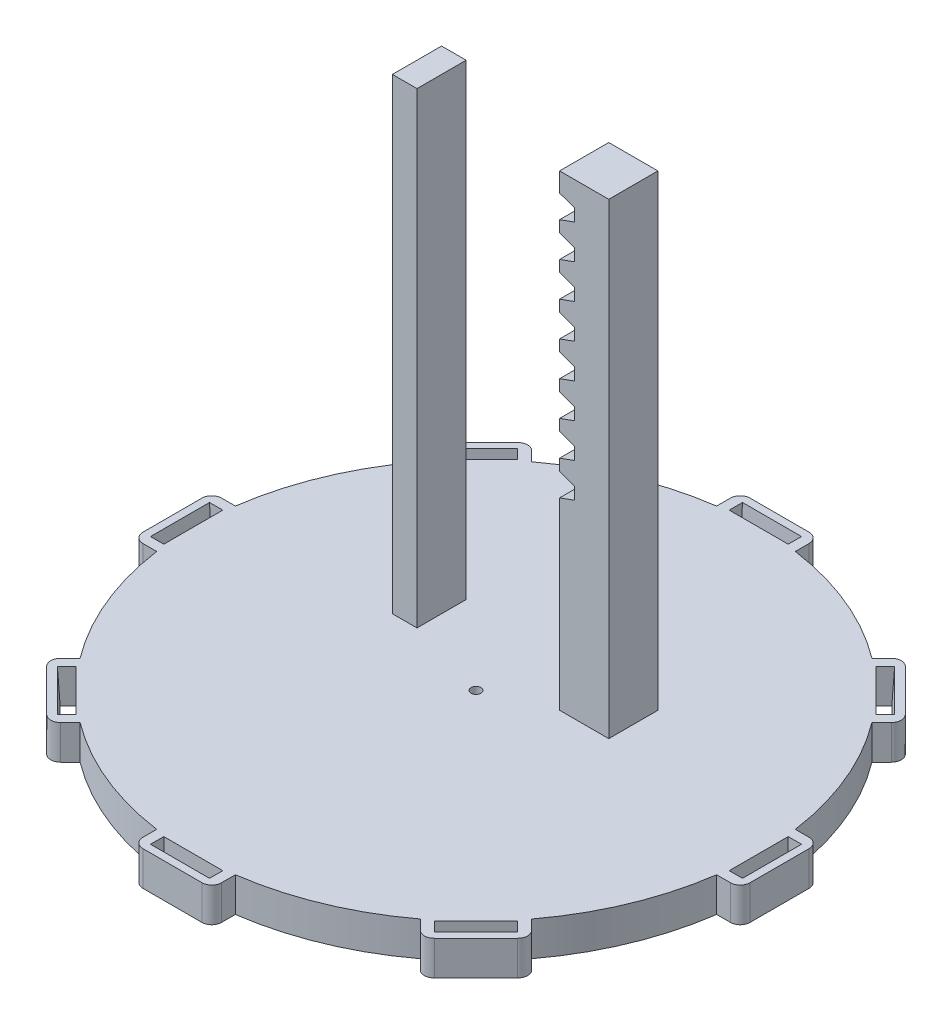
SolidWorks part; units mm, degrees
ref_plane "Front Plane" through (0, 0, 0) normal (0, 0, 1) x (1, 0, 0)
ref_plane "Top Plane" through (0, 0, 0) normal (0, 1, 0) x (1, 0, 0)
ref_plane "Right Plane" through (0, 0, 0) normal (1, 0, 0) x (0, 0, -1)
sketch "Sketch1" plane through (0, 0, 0) normal (0, 1, 0) x (1, 0, 0)
  line L0 (-8, 56.9408) -> (-8, 59.7408)
  line L1 (0, 57.5) -> (0, -57.5) construction
  line L2 (8, 56.9408) -> (8, 59.7408)
  line L3 (-6, 61.7408) -> (6, 61.7408)
  line L4 (39.4147, 47.8999) -> (47.8999, 39.4147)
  line L9 (34.6063, 45.9201) -> (36.5862, 47.8999)
  line L10 (45.9201, 34.6063) -> (47.8999, 36.5862)
  line L15 (61.7408, 6) -> (61.7408, -6)
  line L16 (56.9408, 8) -> (59.7408, 8)
  line L17 (56.9408, -8) -> (59.7408, -8)
  line L22 (47.8999, -39.4147) -> (39.4147, -47.8999)
  line L23 (45.9201, -34.6063) -> (47.8999, -36.5862)
  line L24 (34.6063, -45.9201) -> (36.5862, -47.8999)
  line L29 (6, -61.7408) -> (-6, -61.7408)
  line L30 (8, -56.9408) -> (8, -59.7408)
  line L31 (-8, -56.9408) -> (-8, -59.7408)
  line L36 (-39.4147, -47.8999) -> (-47.8999, -39.4147)
  line L37 (-34.6063, -45.9201) -> (-36.5862, -47.8999)
  line L38 (-45.9201, -34.6063) -> (-47.8999, -36.5862)
  line L43 (-61.7408, -6) -> (-61.7408, 6)
  line L44 (-56.9408, -8) -> (-59.7408, -8)
  line L45 (-56.9408, 8) -> (-59.7408, 8)
  line L50 (-47.8999, 39.4147) -> (-39.4147, 47.8999)
  line L51 (-45.9201, 34.6063) -> (-47.8999, 36.5862)
  line L52 (-34.6063, 45.9201) -> (-36.5862, 47.8999)
  arc A0 (-8, 56.9408) -> (-34.6063, 45.9201) centre (0, 0) ccw
  arc A1 (6, 61.7408) -> (8, 59.7408) centre (6, 59.7408) cw
  arc A2 (-6, 61.7408) -> (-8, 59.7408) centre (-6, 59.7408) ccw
  arc A3 (39.4147, 47.8999) -> (36.5862, 47.8999) centre (38.0005, 46.4857) ccw
  arc A4 (47.8999, 39.4147) -> (47.8999, 36.5862) centre (46.4857, 38.0005) cw
  arc A5 (61.7408, 6) -> (59.7408, 8) centre (59.7408, 6) ccw
  arc A6 (61.7408, -6) -> (59.7408, -8) centre (59.7408, -6) cw
  arc A7 (47.8999, -39.4147) -> (47.8999, -36.5862) centre (46.4857, -38.0005) ccw
  arc A8 (39.4147, -47.8999) -> (36.5862, -47.8999) centre (38.0005, -46.4857) cw
  arc A9 (6, -61.7408) -> (8, -59.7408) centre (6, -59.7408) ccw
  arc A10 (-6, -61.7408) -> (-8, -59.7408) centre (-6, -59.7408) cw
  arc A11 (-39.4147, -47.8999) -> (-36.5862, -47.8999) centre (-38.0005, -46.4857) ccw
  arc A12 (-47.8999, -39.4147) -> (-47.8999, -36.5862) centre (-46.4857, -38.0005) cw
  arc A13 (-61.7408, -6) -> (-59.7408, -8) centre (-59.7408, -6) ccw
  arc A14 (-61.7408, 6) -> (-59.7408, 8) centre (-59.7408, 6) cw
  arc A15 (-47.8999, 39.4147) -> (-47.8999, 36.5862) centre (-46.4857, 38.0005) ccw
  arc A16 (-39.4147, 47.8999) -> (-36.5862, 47.8999) centre (-38.0005, 46.4857) cw
  arc A17 (-45.9201, 34.6063) -> (-56.9408, 8) centre (0, 0) ccw
  arc A18 (-56.9408, -8) -> (-45.9201, -34.6063) centre (0, 0) ccw
  arc A19 (34.6063, 45.9201) -> (8, 56.9408) centre (0, 0) ccw
  arc A20 (-34.6063, -45.9201) -> (-8, -56.9408) centre (0, 0) ccw
  arc A21 (8, -56.9408) -> (34.6063, -45.9201) centre (0, 0) ccw
  arc A22 (45.9201, -34.6063) -> (56.9408, -8) centre (0, 0) ccw
  arc A23 (56.9408, 8) -> (45.9201, 34.6063) centre (0, 0) ccw
  point P11 (8, 61.7408)
  point P14 (-8, 61.7408)
  point P17 (-8, 58.3408)
  point P98 (0, 0)
  dimension "D1" = 115
  dimension "D2" = 2
  dimension "D3" = 16
  dimension "D4" = 2.8
  dimension "D7" = 8
extrude "Boss-Extrude1" add sketch "Sketch1" along normal blind 7
sketch "Sketch2" plane through (0, 7, 0) normal (0, 1, 0) x (1, 0, 0)
  line L0 (-57.5, 0) -> (57.5, 0) construction
  line L1 (0, 0) -> (0, 10) construction
  line L7 (12, 5) -> (22, 5)
  line L14 (0, 10) -> (28.3122, 10) construction
  line L15 (0, 10) -> (-19.5, 10) construction
  line L17 (12, 5) -> (12, 15)
  line L18 (-22, 15) -> (-17, 15)
  line L19 (-22, 15) -> (-22, 5)
  line L20 (-22, 5) -> (-17, 5)
  line L21 (-17, 15) -> (-17, 5)
  line L22 (-22, 15) -> (-17, 5) construction
  line L23 (-22, 5) -> (-17, 15) construction
  line L24 (12, 15) -> (22, 15)
  line L25 (22, 5) -> (22, 15)
  line L26 (12, 5) -> (22, 15) construction
  line L27 (12, 15) -> (22, 5) construction
  circle A0 centre (0, 0) radius 57.5 construction
  point P8 (17, 10)
  dimension "D1" = 10
  dimension "D2" = 29
  dimension "D3" = 12
  dimension "D4" = 10
  dimension "D5" = 10
  dimension "D6" = 5
  dimension "D7" = 10
extrude "Boss-Extrude2" add sketch "Sketch2" along normal blind 95
sketch "Sketch15" plane through (0, 0, 0) normal (0, -1, 0) x (1, 0, 0)
  circle A0 centre (0, 0) radius 1
  dimension "D1" = 2
extrude "Cut-Extrude3" cut sketch "Sketch15" along direction (0, 1, 0) on the side against the normal up to surface (7 mm away) contours A0 up to face at (0, 7, 0)
sketch "Sketch16" plane through (0, 0, 0) normal (0, -1, 0) x (1, 0, 0)
  line L1 (-6, 59.8) -> (6, 59.8)
  line L2 (-6, 59.8) -> (-6, 57.5)
  line L3 (-6, 57.5) -> (6, 57.5)
  line L4 (6, 59.8) -> (6, 57.5)
  point P5 (0, 57.5)
  dimension "D1" = 2.3
  dimension "D2" = 12
  dimension "D3" = 57.5
sketch "Sketch17" plane through (0, 7, 0) normal (0, 1, 0) x (1, 0, 0)
  line L0 (-6, -57.5) -> (6, -57.5) construction
  line L1 (-6, -57.5) -> (6, -57.5)
  line L2 (-6, -57.5) -> (-6, -60.2)
  line L3 (-6, -60.2) -> (6, -60.2)
  line L4 (6, -60.2) -> (6, -57.5)
  dimension "D1" = 2.7
ref_axis "Axis1" through (0, 107.1, 0) along (0, -1, 0)
loft "Cut-Loft2" cut profiles "Sketch16", "Sketch17" connector at (6, 0, 59.8) connector at (6, 7, 60.2)
pattern_circular "CirPattern1" count 8 over 360 about axis through (0, 107.1, 0) along (0, -1, 0) of "Cut-Loft2"
sketch "Sketch18" plane through (0, 0, -15) normal (0, 0, -1) x (-1, 0, 0)
  line L0 (-12, 98.0919) -> (-15, 97)
  line L1 (-12, 102) -> (-12, 7) construction
  line L2 (-15, 97) -> (-15, 94.5)
  line L3 (-15, 95.75) -> (-15.9044, 95.75) construction
  line L4 (-12, 98.0919) -> (-12, 93.4081)
  line L5 (-12, 93.4081) -> (-15, 94.5)
  line L6 (-22, 102) -> (-12, 102) construction
  point P9 (-12, 95.75)
  dimension "D1" = 5
  dimension "D2" = 110
  dimension "D3" = 3
  dimension "D4" = 2.5
extrude "Cut-Extrude4" cut sketch "Sketch18" against normal blind 10
pattern_linear "LPattern1" count 8 spacing 7 along (0, -1, 0) of "Cut-Extrude4"
equation "\"85.00.00mm\"=8500"
